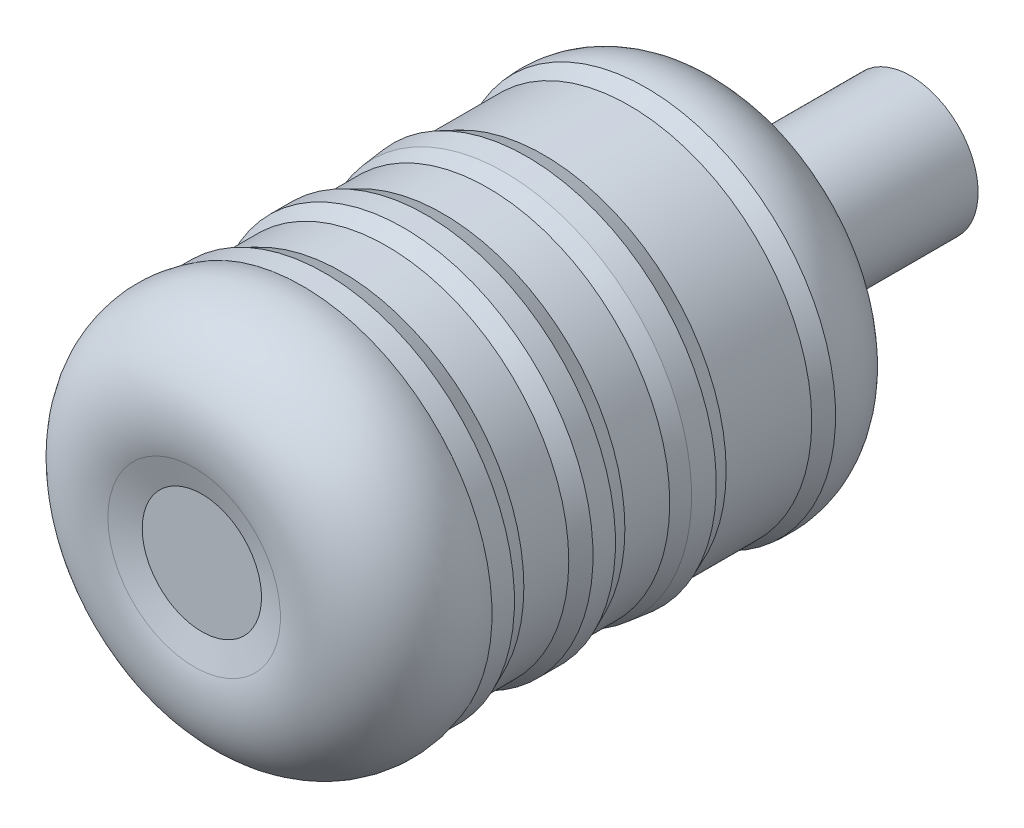
SolidWorks part; units mm, degrees
ref_plane "Front Plane" through (0, 0, 0) normal (0, 0, 1) x (1, 0, 0)
ref_plane "Top Plane" through (0, 0, 0) normal (0, 1, 0) x (1, 0, 0)
ref_plane "Right Plane" through (0, 0, 0) normal (1, 0, 0) x (0, 0, -1)
sketch "Sketch1" plane through (0, 0, 0) normal (0, 1, 0) x (1, 0, 0)
  line L4 (549.7748, 510.7559) -> (549.7748, 403.1725)
  line L5 (559.4107, 393.1791) -> (598.0682, 381.517)
  line L6 (636.7748, 93.2956) -> (636.7748, 77.2956)
  line L7 (636.7748, 322.1725) -> (631.7748, 310.1725)
  line L8 (631.7748, 310.1725) -> (631.7748, 249.1725)
  line L9 (636.7748, 237.1725) -> (631.7748, 249.1725)
  line L10 (636.7748, 237.1725) -> (635.0264, 221.2683)
  line L11 (635.0264, 221.2683) -> (631.4782, 209.2683)
  line L12 (631.4782, 209.2683) -> (631.4782, 177.2956)
  line L13 (631.4782, 177.2956) -> (636.7748, 165.2956)
  line L14 (501.7748, 510.7559) -> (501.7748, 5.5028)
  line L15 (636.7748, 165.2956) -> (636.7748, 149.2956)
  line L16 (636.7748, 149.2956) -> (631.4782, 137.2956)
  line L17 (631.4782, 137.2956) -> (631.4782, 105.2956)
  line L18 (636.7748, 149.2956) -> (631.4782, 137.2956)
  line L20 (631.4782, 105.2956) -> (636.7748, 93.2956)
  line L21 (544.2748, 5.5028) -> (563.2748, 0)
  line L29 (501.7748, 5.5028) -> (544.2748, 5.5028)
  line L32 (549.7748, 510.7559) -> (501.7748, 510.7559)
  arc A0 (549.7748, 403.1725) -> (559.4107, 393.1791) centre (559.7748, 403.1725) ccw
  arc A1 (598.0682, 381.517) -> (636.7748, 322.1725) centre (582.183, 328.8609) cw
  arc A2 (563.2748, 0) -> (636.7748, 77.2956) centre (580.1024, 57.592) ccw
  dimension "D3" = 10
  dimension "D4" = 55
  dimension "D22" = 120
  dimension "D6" = 5
  dimension "D7" = 5
  dimension "D8" = 12
  dimension "D9" = 12
  dimension "D10" = 85
  dimension "D11" = 12
  dimension "D12" = 12
  dimension "D13" = 56
  dimension "D14" = 16
  dimension "D15" = 56
  dimension "D16" = 12
  dimension "D17" = 12
  dimension "D18" = 16
  dimension "D19" = 56
  dimension "D20" = 16
revolve "Revolve2" add sketch "Sketch1" angle 360 about L14 region at (562.7263, 0, -220.4975)
shell "Shell1" thickness 2 removed face at (453.7748, 0, -510.7559)
